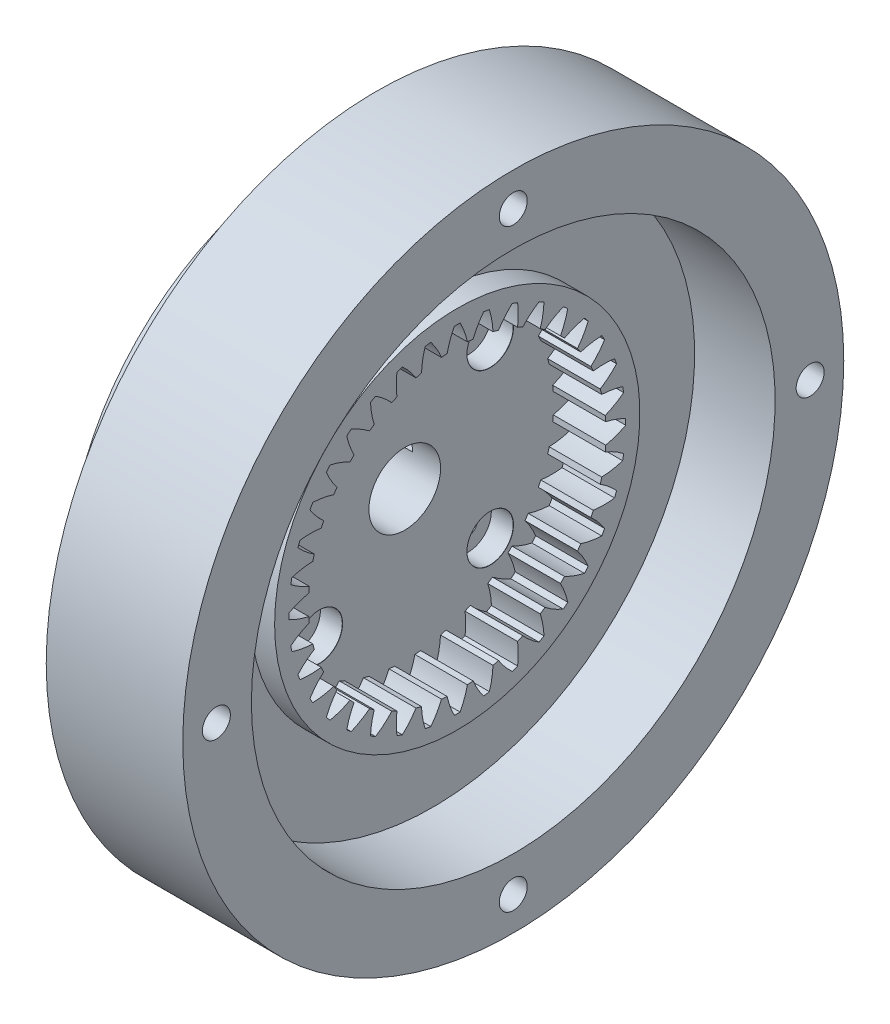
SolidWorks part; units mm, degrees
other "Markup1"
sketch "Sketch48"
ref_plane "Plane1" through (0, 0, 0) normal (0, 0, 1) x (1, 0, 0)
ref_plane "Plane2" through (0, 0, 0) normal (0, 1, 0) x (1, 0, 0)
ref_plane "Plane3" through (0, 0, 0) normal (1, 0, 0) x (0, 0, -1)
sketch "HoldingSke" plane through (0, 0, 0) normal (0, 1, 0) x (1, 0, 0)
  line L0 (0, 0) -> (328.7845, -238.8759)
  line L1 (-15, 0) -> (100, 0) construction
  line L2 (0, 0) -> (-2.1039, 2.3779)
  line L3 (0, 0) -> (-11.863, 4.5341)
  line L4 (0, 0) -> (6.9867, 5.0761)
  line L5 (0, 0) -> (-23.7986, -8.8762)
  line L6 (0, 0) -> (-10.5278, -7.1032)
  line L7 (-2.1039, 2.3779) -> (3.3635, 27.1825)
  line L8 (-76.2, 54.61) -> (-54.61, 54.61)
  line L9 (-67.7845, 28.3722) -> (-49.3413, 33.142)
  line L10 (-76.2, 71.12) -> (104.1128, 71.12)
  line L11 (0, 0) -> (-9.525, 0)
  line L12 (-76.2, 101.6) -> (-76.1428, 101.6)
  line L13 (24.9733, 27.94) -> (52.9518, 28.4284)
  line L14 (24.9733, 27.94) -> (24.9746, 27.94)
  line L15 (24.9733, 27.94) -> (100.4006, 29.5858)
  circle A0 centre (0, 0) radius 12.7
  circle A1 centre (0, 0) radius 12.7
  circle A2 centre (0, 0) radius 12.7
  dimension "MHD" = 25.4
  dimension "Hub_dia" = 25.4
  dimension "Diameter" = 25.4
  dimension "Num_teeth" = 36
  dimension "Pitch" = 406.4
  dimension "Overall_len" = 25.4
  dimension "Show_teeth" = 36
  dimension "Thickness" = 12.7
  dimension "OAL" = 25.4001
  dimension "T_dim" = 21.59
  dimension "Ap" = 14.5
  dimension "H" = 19.05
  dimension "Pitch_radius" = 180.3128
  dimension "Width" = 9.525
  dimension "Backlash" = 0.0571
  dimension "Addendum_fac" = 1
  dimension "Dedendum_fac" = 1.25
  dimension "Clearance_fac" = 0.25
  dimension "Dedendum_add" = 0.0013
sketch "BasProSke" plane through (0, 0, 0) normal (0, 1, 0) x (1, 0, 0)
  line L0 (-10, 0) -> (60, 0) construction
  line L1 (0, 26.9875) -> (0, 30.586)
  line L2 (0, 26.9875) -> (9.525, 26.9875)
  line L3 (9.525, 26.9875) -> (9.525, 30.586)
  line L4 (9.525, 30.586) -> (0, 30.586)
  dimension "Thickness" = 9.525
  dimension "Diameter" = 61.1721
  dimension "Inside_diameter" = 53.975
revolve "Base-Revolve" add sketch "BasProSke" angle 360 about L0
sketch "TooCutSke" plane through (0, 0, 0) normal (1, 0, 0) x (0, 0, -1)
  line L3 (1.3893, 28.5412) -> (1.3893, 53.6633) construction
  line L4 (0, 0) -> (0, 59.563) construction
  line L5 (0, 0) -> (-5.9551, 68.0675) construction
  line L6 (-12.1342, 23.9318) -> (35.5288, 28.1018) construction
  circle A0 centre (0, 0) radius 28.575 construction
  circle A1 centre (0, 0) radius 30.5606 construction
  circle A2 centre (0, 0) radius 24.8983 construction
  circle A3 centre (0, 0) radius 26.9621 construction
  arc A4 (1.8417, 26.8991) -> (0.5248, 30.5561) centre (-12.1342, 23.9318) ccw
  arc A5 (1.8417, 26.8991) -> (-1.8417, 26.8991) centre (0, 0) ccw
  arc A6 (0.5248, 30.5561) -> (-0.5248, 30.5561) centre (0, 0) ccw
  arc A7 (-0.5248, 30.5561) -> (-1.8417, 26.8991) centre (12.1342, 23.9318) ccw
  dimension "Pitch_dia" = 57.15
  dimension "Base_dia" = 49.7967
  dimension "Root_dia" = 61.1213
  dimension "Overcut_dia" = 53.9242
  dimension "Flank_rad" = 14.2875
  dimension "Half_ang" = 5
  dimension "Half_CT" = 1.3893
extrude "ToothCut" cut sketch "TooCutSke" along normal through all
fillet "Breaks" [suppressed] radius 0.1588
fillet "RootFillets" [suppressed] radius 0.3981
pattern_circular "TeethCuts" count 36 over 360 about axis through (-10, 0, 0) along (1, 0, 0) of "RootFillets", "Breaks", "ToothCut"
sketch "Sketch3" plane through (0, 0, 0) normal (1, 0, 0) x (0, 0, -1)
  circle A0 centre (0, 0) radius 30.586 construction
  circle A1 centre (0, 0) radius 30.586
extrude "Extrude-Thin1" add sketch "Sketch3" along normal up to surface (9.525 mm away) thin up to face at (9.525, 0, 30.586) thin type one direction wall 2.54
sketch "Sketch4" plane through (0, 0, 0) normal (1, 0, 0) x (0, 0, -1)
  circle A0 centre (0, 0) radius 33.126 construction
  circle A1 centre (0, 0) radius 33.126
extrude "Extrude-Thin2" add sketch "Sketch4" along normal blind 5.08 thin thin type one direction wall 6.35
sketch "Sketch5" plane through (0, 0, 0) normal (1, 0, 0) x (0, 0, -1)
  circle A0 centre (0, 0) radius 28.575 construction
  dimension "D1" = 57.15
sketch "Sketch9" plane through (0, 0, 0) normal (-1, 0, 0) x (0, 0, 1)
  circle A0 centre (0, 0) radius 59.944
  circle A1 centre (0, 0) radius 39.476 construction
  circle A2 centre (0, 0) radius 39.476
  dimension "D1" = 119.888
extrude "Boss-Extrude2" add sketch "Sketch9" against normal up to surface (5.08 mm away) up to face at (5.08, 0, -39.476)
sketch "Sketch12" plane through (0, 0, 0) normal (-1, 0, 0) x (0, 0, 1)
  circle A23 centre (0, 0) radius 59.944
  circle A43 centre (0, 0) radius 59.944
  dimension "D1" = 0
extrude "Boss-Extrude3" add sketch "Sketch12" along normal blind 5.08 contours A43
sketch "Sketch13" plane through (0, 0, 0) normal (1, 0, 0) x (0, 0, -1)
  circle A0 centre (0, 0) radius 20.2565
  circle A1 centre (0, 0) radius 17.9705
  dimension "D1" = 40.513
  dimension "D2" = 35.941
extrude "Cut-Extrude10" cut sketch "Sketch13" against normal blind 2.032
sketch "Sketch14" plane through (-5.08, 0, 0) normal (-1, 0, 0) x (0, 0, 1)
  circle A0 centre (0, 0) radius 3.302
  dimension "D1" = 6.604
extrude "Cut-Extrude11" cut sketch "Sketch14" against normal through all both and the other way through all
sketch "Sketch15" plane through (5.08, 0, 0) normal (1, 0, 0) x (0, 0, -1)
  circle A0 centre (0, 0) radius 47.498
  circle A1 centre (0, 0) radius 59.944 construction
  circle A2 centre (0, 0) radius 59.944
  dimension "D1" = 12.446
extrude "Boss-Extrude5" add sketch "Sketch15" along normal blind 14.605
sketch "Sketch16" plane through (19.685, 0, 0) normal (1, 0, 0) x (0, 0, -1)
  line L0 (0, 56.388) -> (0, 59.944) construction
  line L1 (0, 51.308) -> (0, 47.498) construction
  line L2 (56.388, 0) -> (59.944, 0) construction
  line L3 (51.308, 0) -> (47.498, 0) construction
  line L4 (0, -56.388) -> (0, -59.944) construction
  line L5 (0, -51.308) -> (0, -47.498) construction
  line L6 (-56.388, 0) -> (-59.944, 0) construction
  line L7 (-51.308, 0) -> (-47.498, 0) construction
  line L8 (0, 0) -> (-47.498, 0) construction
  circle A2 centre (0, 0) radius 59.944 construction
  circle A3 centre (0, 53.848) radius 2.54 construction
  circle A4 centre (0, 0) radius 47.498 construction
  circle A5 centre (53.848, 0) radius 2.54 construction
  circle A6 centre (0, -53.848) radius 2.54 construction
  circle A7 centre (-53.848, 0) radius 2.54 construction
  point P4 (0, 56.388)
  point P19 (56.388, 0)
  point P26 (0, -56.388)
  point P33 (-56.388, 0)
  point P38 (0, 0)
  dimension "D2" = 5.08
  dimension "D1" = 53.848
  dimension "D3" = 4
hole_wizard "CBORE for #00 Binding Head Machine Screw1" positions "Sketch18" profile "Sketch19" counterbore size "#00" standard "ANSI Inch" end condition through all
sketch "Sketch18" plane through (-5.08, 0, 0) normal (-1, 0, 0) x (0, 0, 1)
  point P0 (0, 53.848)
  point P3 (53.848, 0)
  point P6 (0, -53.848)
  point P9 (-53.848, 0)
sketch "Sketch19" plane through (-5.08, 53.848, 0) normal (0, 1, 0) x (0, 0, 1)
  line L0 (0, 0) -> (0, 24.765)
  line L1 (0, 24.765) -> (2.54, 24.765)
  line L3 (2.54, 24.765) -> (2.54, 1.27)
  line L4 (2.54, 1.27) -> (3.81, 1.27)
  line L5 (3.81, 1.27) -> (3.81, 0)
  line L7 (3.81, 0) -> (0, 0)
  line L11 (0, -6.35) -> (0, 107.95) construction
  dimension "Thru Hole Dia." = 5.08
  dimension "Thru Hole Depth" = 24.765
  dimension "C'Bore Dia." = 7.62
  dimension "C'Bore Depth" = 1.27
sketch "Sketch21" plane through (-5.08, 0, 0) normal (-1, 0, 0) x (0, 0, 1)
  circle A0 centre (0, 0) radius 19.05
  dimension "D1" = 38.1
extrude "Cut-Extrude12" cut sketch "Sketch21" against normal blind 1.524
sketch "Sketch22" plane through (-5.08, 0, 0) normal (-1, 0, 0) x (0, 0, 1)
  circle A0 centre (15.5, -15.5) radius 1.5 construction
  circle A1 centre (-15.5, -15.5) radius 1.5 construction
  circle A2 centre (-15.5, 15.5) radius 1.5 construction
  circle A3 centre (15.5, 15.5) radius 1.5 construction
  circle A5 centre (0, 0) radius 3.302 construction
  dimension "D1" = 31
  dimension "D4" = 15.5
  dimension "D5" = 3
  dimension "D2" = 31
  dimension "D3" = 15.5
sketch "Sketch26" plane through (-3.556, 0, 0) normal (-1, 0, 0) x (0, 0, 1)
  circle A0 centre (0, 0) radius 7.62
  dimension "D1" = 15.24
extrude "Cut-Extrude15" cut sketch "Sketch26" against normal through all
sketch "Sketch28" plane through (-3.556, 0, 0) normal (-1, 0, 0) x (0, 0, 1)
  circle A1 centre (0, 0) radius 19.05
  circle A2 centre (0, 0) radius 19.05
  circle M2 centre (0, 0) radius 7.62
  circle M3 centre (0, 0) radius 19.05
  dimension "D1" = 0
extrude "Boss-Extrude8" add sketch "Sketch28" along normal up to surface (1.524 mm away) contours M3 M2 region at (-3.556, 0, -18.5112) up to face at (-5.08, 0, 19.05)
sketch "Sketch29" plane through (-5.08, 0, 0) normal (-1, 0, 0) x (0, 0, 1)
  circle A0 centre (0, 0) radius 44.45
  dimension "D1" = 88.9
extrude "Boss-Extrude9" add sketch "Sketch29" along normal blind 11.62
sketch "Sketch31" plane through (-16.7, 0, 0) normal (-1, 0, 0) x (0, 0, 1)
  line L0 (0, 0) -> (0, 59.944) construction
  line L2 (-7.62, 0) -> (7.62, 0)
  line L3 (-7.62, 0) -> (-7.62, 50.8)
  line L4 (-7.62, 50.8) -> (7.62, 50.8)
  line L5 (7.62, 0) -> (7.62, 50.8)
  line L6 (-7.62, 0) -> (7.62, 50.8) construction
  line L7 (-7.62, 50.8) -> (7.62, 0) construction
  circle A0 centre (0, 0) radius 59.944 construction
  circle A1 centre (0, 0) radius 7.62 construction
  point P6 (0, 25.4)
  dimension "D1" = 50.8
  dimension "D2" = 0
extrude "Cut-Extrude17" cut sketch "Sketch31" against normal up to surface (11.62 mm away) up to face at (-5.08, 0, 44.45)
sketch "Sketch32" plane through (-16.7, 0, 0) normal (-1, 0, 0) x (0, 0, 1)
  circle A0 centre (0, 0) radius 11.5
  dimension "D1" = 23
extrude "Cut-Extrude18" cut sketch "Sketch32" against normal blind 2
sketch "Sketch34" plane through (0, 0, 0) normal (1, 0, 0) x (0, 0, -1)
  line L3 (-11.3722, 58.8554) -> (-50.8, 51.237)
  line L4 (-11.3722, -58.8554) -> (-50.8, -51.237)
  line L5 (0, 0) -> (-203.2, 0) construction
  line L6 (-203.2, 41.275) -> (-203.2, -41.275)
  arc A0 (-203.2, -41.275) -> (-50.8, -51.237) centre (-166.4499, -649.7662) cw
  circle A2 centre (0, 0) radius 59.944 construction
  arc A3 (-203.2, 41.275) -> (-50.8, 51.237) centre (-166.4499, 649.7662) ccw
  arc A4 (-11.3722, 58.8554) -> (-11.3722, -58.8554) centre (0, 0) ccw
  point P12 (-203.2, 0)
  dimension "D2" = 609.6
  dimension "D1" = 203.2
  dimension "D3" = 82.55
  dimension "D4" = 50.8
sketch "Sketch38" plane through (-2.032, 0, 0) normal (1, 0, 0) x (0, 0, -1)
  circle A1 centre (0, 0) radius 20.2565
  circle A2 centre (0, 0) radius 20.2565
  circle M2 centre (0, 0) radius 17.9705
  circle M3 centre (0, 0) radius 20.2565
  dimension "D1" = 0
extrude "Boss-Extrude14" add sketch "Sketch38" along normal up to surface (2.032 mm away) contours M3 M2 region at (-2.032, 0, 19.6836) up to face at (0, 0, -20.2565)
hole_wizard "CBORE for M3 Hex Head Machine Screw1" positions "Sketch39" profile "Sketch40" counterbore size "M3" standard "ANSI Metric" end condition through all
sketch "Sketch39" plane through (0, 0, 0) normal (1, 0, 0) x (0, 0, -1)
  point P0 (15.5, 15.5)
  point P3 (-15.5, 15.5)
  point P6 (-15.5, -15.5)
  point P9 (15.5, -15.5)
sketch "Sketch40" plane through (0, 15.5, -15.5) normal (0, 1, 0) x (0, 0, -1)
  line L0 (0, 0) -> (0, 16.7)
  line L1 (0, 16.7) -> (1.7, 16.7)
  line L3 (1.7, 16.7) -> (1.7, 4)
  line L4 (4.2, 4) -> (1.7, 4)
  line L5 (4.2, 4) -> (4.2, 0.025)
  line L6 (4.2, 0.025) -> (4.225, 0)
  line L7 (4.225, 0) -> (0, 0)
  line L8 (-4.2, 0.025) -> (-4.225, 0) construction
  line L11 (0, -6.35) -> (0, 107.95) construction
  dimension "Thru Hole Dia." = 3.4
  dimension "Thru Hole Depth" = 16.7
  dimension "C'Bore Dia." = 8.4
  dimension "C'Bore Depth" = 4
  dimension "Near C'Sink Dia." = 8.45
  dimension "Near C'Sink Angle" = 90
sketch "Sketch41" plane through (-5.08, 0, 0) normal (1, 0, 0) x (0, 0, -1)
  circle A0 centre (0, 0) radius 7.62 construction
  circle A1 centre (0, 0) radius 7.62
extrude "Cut-Extrude21" cut sketch "Sketch41" against normal through all
sketch "Sketch42" plane through (0, 0, 0) normal (1, 0, 0) x (0, 0, -1)
  circle A0 centre (0, 0) radius 3
  circle A1 centre (0, 0) radius 7.62 construction
  circle A2 centre (0, 0) radius 7.62
  dimension "D1" = 6
extrude "Boss-Extrude15" add sketch "Sketch42" against normal up to surface (14.7 mm away) contours A2 A0 region at (0, 0, 7.4045) up to face at (-14.7, -2.6267, 0)
sketch "Sketch43" plane through (-5.08, 0, 0) normal (-1, 0, 0) x (0, 0, 1)
  line L0 (-7.62, 0) -> (-7.62, 8.6131) construction
  line L1 (7.62, 43.792) -> (7.62, 0) construction
  line L2 (-7.62, 0) -> (-7.62, 8.6131)
  line L3 (7.62, 8.6131) -> (7.62, 0)
  arc A1 (7.62, 8.6131) -> (-7.62, 8.6131) centre (0, 0) ccw
  arc A4 (-7.62, 8.6131) -> (7.62, 8.6131) centre (0, 0) ccw construction
  arc A5 (7.62, 0) -> (-7.62, 0) centre (0, 0) ccw construction
  arc A6 (7.62, 0) -> (-7.62, 0) centre (0, 0) ccw
extrude "Boss-Extrude16" add sketch "Sketch43" along normal up to surface (9.62 mm away) up to face at (-14.7, 1.1833, 0)
sketch "Sketch45" plane through (-14.7, 0, 0) normal (-1, 0, 0) x (0, 0, 1)
  line L0 (0, 0) -> (47.498, 0) construction
  line L1 (-3, 0) -> (3, 0)
  line L2 (-3, 0) -> (-3, 25.4)
  line L3 (-3, 25.4) -> (3, 25.4)
  line L4 (3, 0) -> (3, 25.4)
  circle A0 centre (0, 0) radius 3 construction
  dimension "D1" = 25.4
extrude "Cut-Extrude22" cut sketch "Sketch45" against normal up to surface (9.62 mm away) up to face at (-5.08, 53.848, 3.81)
sketch "Sketch46" plane through (-5.08, 0, 0) normal (-1, 0, 0) x (0, 0, 1)
  line L0 (7.62, 43.792) -> (7.62, 8.6131) construction
  line L1 (7.62, 26.2025) -> (-7.62, 26.2025)
  line L2 (7.62, 26.2025) -> (7.62, 0)
  line L3 (7.62, 0) -> (-7.62, 0)
  line L4 (-7.62, 26.2025) -> (-7.62, 0)
  line L5 (-7.62, 43.792) -> (-7.62, 8.6131) construction
  line L7 (0, 0) -> (47.498, 0) construction
extrude "Cut-Extrude23" cut sketch "Sketch46" along normal up to surface (9.62 mm away) up to face at (-14.7, 2.8085, 0)
sketch "Sketch47" plane through (0, 0, 0) normal (1, 0, 0) x (0, 0, -1)
  circle A0 centre (0, 0) radius 6.5
  dimension "D1" = 13
extrude "Cut-Extrude24" cut sketch "Sketch47" against normal up to surface (14.7 mm away) up to face at (-14.7, -0.9811, 0)
sketch "Sketch49" plane through (19.685, 0, 0) normal (1, 0, 0) x (0, 0, -1)
  line L0 (0, 0) -> (0, 171.45) construction
  line L1 (-59.992, 160.6295) -> (-55.4107, 135.2295)
  line L4 (-59.1113, 9.9568) -> (-54.8329, 35.3568)
  line L7 (59.1113, 9.9568) -> (54.8329, 35.3568)
  line L8 (59.992, 160.6295) -> (55.4107, 135.2295)
  line L9 (-50.8, 85.3182) -> (50.8, 85.3182) construction
  circle A4 centre (0, 0) radius 59.944 construction
  arc A5 (59.944, 0) -> (59.1113, 9.9568) centre (0, 0) ccw construction
  arc A6 (59.992, 160.6295) -> (-59.992, 160.6295) centre (0, 171.45) ccw
  arc A7 (-54.8329, 35.3568) -> (-55.4107, 135.2295) centre (-341.4575, 83.6365) ccw
  arc A8 (54.8329, 35.3568) -> (55.4107, 135.2295) centre (341.4575, 83.6365) cw
  arc A9 (59.1113, 9.9568) -> (-59.1113, 9.9568) centre (0, 0) ccw
  arc A10 (-59.1113, 9.9568) -> (59.944, 0) centre (0, 0) ccw construction
  arc A11 (-59.1113, 9.9568) -> (59.944, 0) centre (0, 0) ccw construction
  arc A12 (59.944, 0) -> (59.1113, 9.9568) centre (0, 0) ccw construction
  dimension "D2" = 25.4
  dimension "D3" = 101.6
  dimension "D1" = 25.4
  dimension "D5" = 60.96
  dimension "D4" = 171.45
fillet "Fillet1" radius 2.54 1 edges at (-5.08, -44.45, 0)
equation "' \"Pitch@HoldingSke\" = 4"
equation "' \"Num_teeth@HoldingSke\" = 24"
equation "' \"Ap@HoldingSke\" =  14.5"
equation "' \"Ap@HoldingSke\" = 14.5"
equation "' \"Width@HoldingSke\" = 0.5"
equation "' \"Diameter@HoldingSke\" = 8"
equation "' \"Show_teeth@HoldingSke\" = 100"
equation "' \"Backlash@HoldingSke\" = 0.009"
equation "' \"Addendum_fac@HoldingSke\" = 1.0"
equation "' \"Dedendum_fac@HoldingSke\" = 1.25"
equation "' \"Dedendum_add@HoldingSke\" = 0.00005"
equation "' \"Clearance_fac@HoldingSke\" = 0.25"
equation "\"Overcut_dia@TooCutSke\" = (\"Num_teeth@HoldingSke\" - 2 * \"Addendum_fac@HoldingSke\") / \"Pitch@HoldingSke\" - 0.002"
equation "\"Pitch_dia@TooCutSke\" = \"Num_teeth@HoldingSke\" / \"Pitch@HoldingSke\""
equation "\"Base_dia@TooCutSke\" = \"Num_teeth@HoldingSke\" / \"Pitch@HoldingSke\" * cos((\"Ap@HoldingSke\"  * 3.14159265 / 180)) * 0.90"
equation "\"Root_dia@TooCutSke\" = \"Num_teeth@HoldingSke\"  / \"Pitch@HoldingSke\" + 2 *  \"Dedendum_fac@HoldingSke\"/ \"Pitch@HoldingSke\" + \"Dedendum_add@HoldingSke\" * 2"
equation "\"Half_ang@TooCutSke\" = 180 / \"Num_teeth@HoldingSke\""
equation "\"Half_CT@TooCutSke\" = \"Num_teeth@HoldingSke\" / \"Pitch@HoldingSke\" * sin((3.14159265 / 2 / \"Num_teeth@HoldingSke\")) / 2 + 10 * \"Backlash@HoldingSke\" / 4"
equation "\"Flank_rad@TooCutSke\" = \"Num_teeth@HoldingSke\" / \"Pitch@HoldingSke\" / 4"
equation "\"Radius@RootFillets\"= \"Clearance_fac@HoldingSke\" / \"Pitch@HoldingSke\" + \"Dedendum_add@HoldingSke\""
equation "\"Break_rad@Breaks\" = 0.02 / \"Pitch@HoldingSke\" * 5"
equation "\"Num_teeth@TeethCuts\" = int( \"Show_teeth@HoldingSke\" ) + 1"
equation "\"Num_teeth@TeethCuts\" = ((sgn( \"Num_teeth@TeethCuts\" - \"Num_teeth@HoldingSke\" )-1)*( \"Num_teeth@TeethCuts\" - \"Num_teeth@HoldingSke\" ))/-2+ \"Num_teeth@HoldingSke\""
equation "\"Num_teeth@TeethCuts\" = ((sgn( \"Num_teeth@TeethCuts\" - 2.0)+1)*( \"Num_teeth@TeethCuts\" - 2.0))/2 +2.0"
equation "\"Angle@TeethCuts\" = 360.0 / \"Num_teeth@HoldingSke\""
equation "\"Diameter@BasProSke\" = \"Num_teeth@HoldingSke\"  / \"Pitch@HoldingSke\" + 2 *  \"Dedendum_fac@HoldingSke\"/ \"Pitch@HoldingSke\" + \"Dedendum_add@HoldingSke\" * 2 + 0.002"
equation "\"Diameter@BasProSke\" = ((sgn( \"Diameter@BasProSke\"  - \"Diameter@HoldingSke\" )+1)*( \"Diameter@BasProSke\"  - \"Diameter@HoldingSke\" ))/2 + \"Diameter@HoldingSke\""
equation "\"Inside_diameter@BasProSke\" =  (\"Num_teeth@HoldingSke\" - 2 * \"Addendum_fac@HoldingSke\") / \"Pitch@HoldingSke\" "
equation "\"Thickness@BasProSke\"  = \"Width@HoldingSke\""
